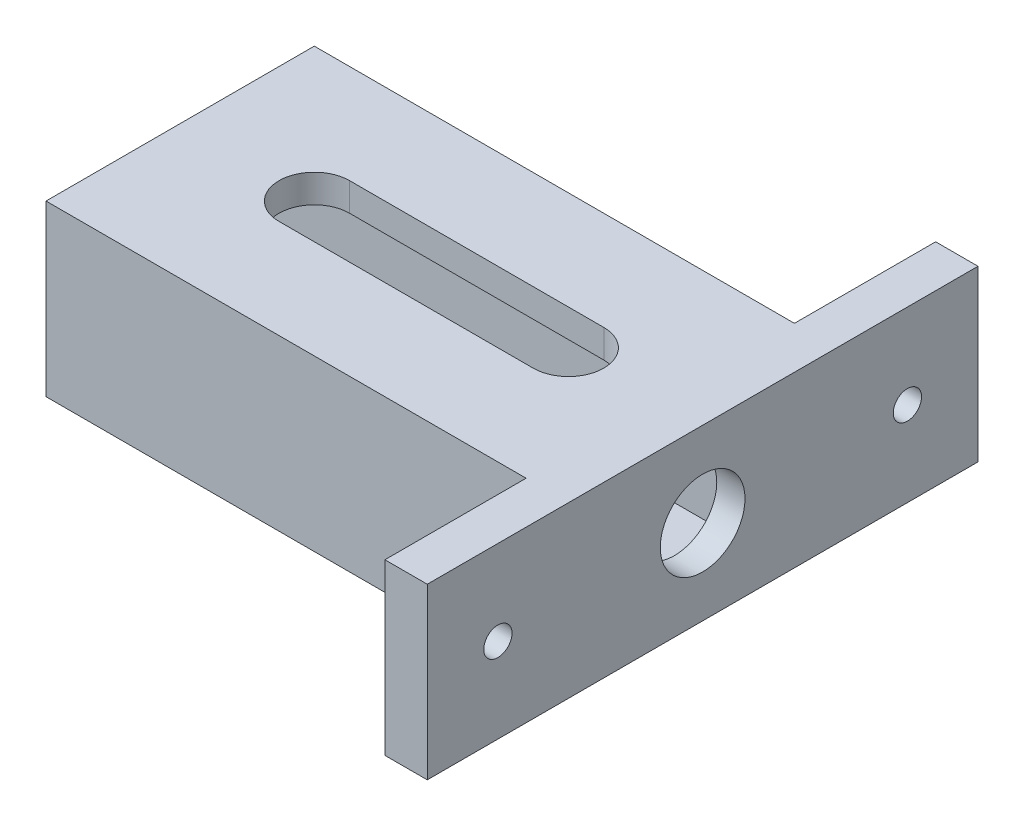
SolidWorks part; units mm, degrees
ref_plane "Front Plane" through (0, 0, 0) normal (0, 0, 1) x (1, 0, 0)
ref_plane "Top Plane" through (0, 0, 0) normal (0, 1, 0) x (1, 0, 0)
ref_plane "Right Plane" through (0, 0, 0) normal (1, 0, 0) x (0, 0, -1)
sketch "Croquis1" plane through (0, 0, 0) normal (0, 1, 0) x (1, 0, 0)
  line L0 (-16.5, -7.5) -> (-18.5, -7.5)
  line L1 (16.5, 7.5) -> (-16.5, 7.5)
  line L2 (16.5, 7.5) -> (16.5, -7.5)
  line L3 (16.5, -7.5) -> (-16.5, -7.5)
  line L4 (-16.5, 7.5) -> (-16.5, -7.5)
  line L5 (16.5, 7.5) -> (-16.5, -7.5) construction
  line L6 (16.5, -7.5) -> (-16.5, 7.5) construction
  line L7 (18.5, -9.5) -> (-18.5, -9.5)
  line L8 (18.5, -9.5) -> (18.5, 9.5)
  line L9 (18.5, 9.5) -> (-18.5, 9.5)
  line L10 (-18.5, -9.5) -> (-18.5, 9.5)
  line L11 (18.5, -9.5) -> (-18.5, 9.5) construction
  line L12 (18.5, 9.5) -> (-18.5, -9.5) construction
  line L13 (-16.5, 7.5) -> (-18.5, 7.5)
  point P0 (0, 0)
  point P6 (0, 0)
  dimension "D1" = 33
  dimension "D2" = 15
  dimension "D3" = 2
  dimension "D4" = 2
extrude "Saliente-Extruir1" add sketch "Croquis1" along normal blind 2 contours L1 L4 L3 L2 | L4 L13 L10 L0 region at (0, 0, 0) region at (-17.5, 0, 0)
extrude "Saliente-Extruir2" add sketch "Croquis1<4>" along normal blind 10 contours L13 L1 L2 L3 L0 L10 L7 L8 L9 region at (0, 0, 7.9159)
sketch "Croquis1<4>" plane through (0, 0, 0) normal (0, 1, 0) x (1, 0, 0) same geometry as "Croquis1"
sketch "Croquis2" plane through (0, 10, 0) normal (0, 1, 0) x (1, 0, 0)
  line L0 (18.5, -9.5) -> (-18.5, -9.5)
  line L1 (-18.5, -9.5) -> (-18.5, 9.5)
  line L2 (-18.5, 9.5) -> (18.5, 9.5)
  line L3 (18.5, 9.5) -> (18.5, -9.5)
extrude "Saliente-Extruir3" add sketch "Croquis2" along normal blind 2
sketch "Croquis4" plane through (0, 0, 0) normal (0, -1, 0) x (-1, 0, 0)
  line L0 (-18.5, 0) -> (18.5, 0) construction
  line L1 (-18.5, -9.5) -> (-18.5, 9.5) construction
  line L2 (18.5, -9.5) -> (18.5, 9.5) construction
  circle A0 centre (11.5, 0) radius 1.6
  dimension "D2" = 3.2
  dimension "D1" = 30
extrude "Cortar-Extruir2" [suppressed] cut sketch "Croquis4" against normal blind 34
sketch "Croquis7" plane through (0, 12, 0) normal (0, 1, 0) x (1, 0, 0)
  line L0 (18.5, 9.5) -> (-18.5, 9.5) construction
  line L1 (18.5, 0) -> (-9, 0) construction
  line L3 (-9, 2.5) -> (9, 2.5)
  line L4 (-9, -2.5) -> (9, -2.5)
  line L5 (0, 0) -> (0, -4.4521) construction
  arc A0 (-9, 2.5) -> (-9, -2.5) centre (-9, 0) ccw
  arc A1 (9, 2.5) -> (9, -2.5) centre (9, 0) cw
  point P15 (0, -2.5)
  point P17 (0, 2.5)
  dimension "D3" = 5
  dimension "D1" = 27.5
  dimension "D2" = 9.5
  dimension "D4" = 9.5
  dimension "D5" = 18.5
extrude "Cortar-Extruir4" cut sketch "Croquis7" against normal blind 3 contours A0 region at (0, 12, 0)
sketch "Croquis8" plane through (0, 0, -9.5) normal (0, 0, -1) x (-1, 0, 0)
  line L0 (-18.5, 0) -> (-15.5, 0)
  line L1 (-18.5, 0) -> (18.5, 0) construction
  line L2 (-15.5, 0) -> (-15.5, 12)
  line L3 (-18.5, 12) -> (18.5, 12) construction
  line L4 (-15.5, 12) -> (-18.5, 12)
  line L5 (-18.5, 12) -> (-18.5, 0)
  dimension "D1" = 3
extrude "Saliente-Extruir5" add sketch "Croquis8" along normal blind 10
sketch "Croquis9" plane through (15.5, 0, 0) normal (-1, 0, 0) x (0, 0, 1)
  line L0 (-9.5, 0) -> (-9.5, 12) construction
  line L2 (-19.5, 0) -> (-9.5, 0) construction
  circle A0 centre (-14.5, 6) radius 1
  dimension "D1" = 2
  dimension "D2" = 5
  dimension "D3" = 6
extrude "Cortar-Extruir5" cut sketch "Croquis9" against normal blind 10
mirror "Simetría3" about plane through (0, 0, 0) normal (0, 0, 1) of "Saliente-Extruir5", "Cortar-Extruir5"
sketch "Croquis10" plane through (16.5, 0, 0) normal (-1, 0, 0) x (0, 0, 1)
  line L0 (-7.5, 2) -> (-7.5, 10)
  line L1 (-7.5, 10) -> (-4.25, 10)
  line L2 (-4.25, 10) -> (-4.25, 2)
  line L3 (-7.5, 2) -> (7.5, 2) construction
  line L4 (-4.25, 2) -> (-7.5, 2)
  line L5 (0, 0) -> (0, 15.9329) construction
  line L6 (7.5, 10) -> (4.25, 10)
  line L7 (4.25, 10) -> (4.25, 2)
  line L8 (7.5, 2) -> (7.5, 10)
  line L9 (4.25, 2) -> (7.5, 2)
  dimension "D1" = 3.25
extrude "Saliente-Extruir6" add sketch "Croquis10" along normal blind 35
sketch "Croquis11" plane through (18.5, 0, 0) normal (1, 0, 0) x (0, 0, -1)
  line L0 (-19.5, 0) -> (19.5, 0) construction
  line L1 (19.5, 12) -> (19.5, 0) construction
  circle A0 centre (0, 6) radius 3
  dimension "D1" = 6
  dimension "D2" = 6
  dimension "D3" = 19.5
extrude "Cortar-Extruir6" cut sketch "Croquis11" against normal blind 35
sketch "Croquis12" plane through (0, 0, 0) normal (0, -1, 0) x (1, 0, 0)
  line L0 (-18.5, 9.5) -> (-18.5, -9.5) construction
  line L1 (15.5, 9.5) -> (-18.5, 9.5) construction
  circle A0 centre (-8.5, 0) radius 1.25
  dimension "D2" = 2.5
  dimension "D3" = 9.5
  dimension "D1" = 10
extrude "Cortar-Extruir7" cut sketch "Croquis12" against normal blind 5
